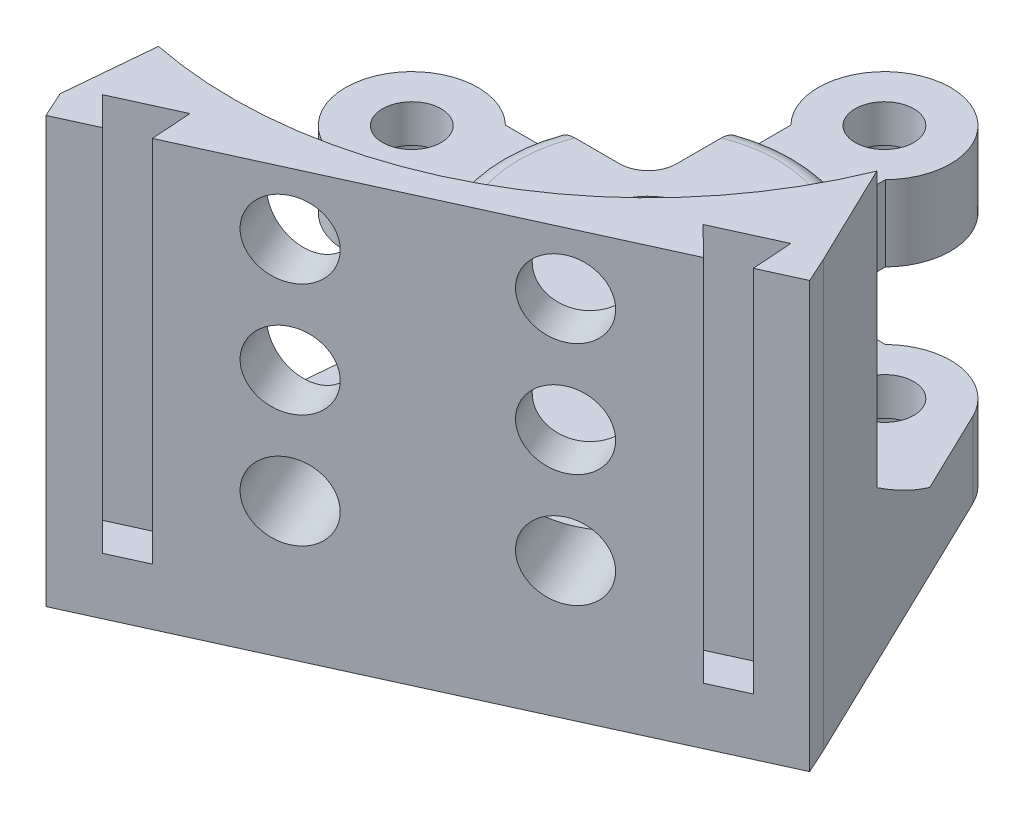
SolidWorks part; units mm, degrees
material "Nylon 6/10"
ref_plane "Front Plane" through (0, 0, 0) normal (0, 0, 1) x (1, 0, 0)
ref_plane "Top Plane" through (0, 0, 0) normal (0, 1, 0) x (1, 0, 0)
ref_plane "Right Plane" through (0, 0, 0) normal (1, 0, 0) x (0, 0, -1)
sketch "Sketch1" plane through (0, 0, 0) normal (0, 1, 0) x (1, 0, 0)
  line L0 (-5, 5) -> (-5, 25)
  line L1 (-25, -5) -> (-5, -5)
  line L2 (-25, -5) -> (-25, 5)
  line L3 (-25, 5) -> (-5, 5)
  line L4 (25, -5) -> (25, 5)
  line L5 (-25, -5) -> (25, 5) construction
  line L6 (-25, 5) -> (25, -5) construction
  line L7 (-5, -25) -> (5, -25)
  line L8 (-5, -25) -> (-5, -5)
  line L9 (-5, 25) -> (5, 25)
  line L10 (5, -25) -> (5, -5)
  line L11 (-5, -25) -> (5, 25) construction
  line L12 (-5, 25) -> (5, -25) construction
  line L13 (5, 5) -> (25, 5)
  line L14 (5, 5) -> (5, 25)
  line L15 (5, -5) -> (25, -5)
  point P0 (0, 0)
  point P6 (0, 0)
  dimension "D1" = 10
  dimension "D2" = 10
  dimension "D3" = 50
  dimension "D4" = 50
extrude "Boss-Extrude1" add sketch "Sketch1" along normal blind 8
sketch "Sketch2" plane through (0, 8, 0) normal (0, 1, 0) x (1, 0, 0)
  line L0 (25, -5) -> (25, 5) construction
  circle A0 centre (25, 0) radius 7
  circle A1 centre (0, -25) radius 7
  circle A2 centre (-25, 0) radius 7
  circle A3 centre (0, 25) radius 7
  point P13 (0, 0)
  dimension "D1" = 14
  dimension "D2" = 4
extrude "Boss-Extrude2" add sketch "Sketch2" against normal up to surface (8 mm away) up to face at (0, 0, 0)
sketch "Sketch3" plane through (0, 8, 0) normal (0, 1, 0) x (1, 0, 0)
  circle A0 centre (25, 0) radius 3.1
  circle A1 centre (0, -25) radius 3.1
  circle A2 centre (-25, 0) radius 3.1
  circle A3 centre (0, 25) radius 3.1
  point P12 (0, 0)
  dimension "D1" = 6.2
  dimension "D2" = 4
extrude "Cut-Extrude1" cut sketch "Sketch3" against normal up to surface (8 mm away) up to face at (0, 0, 0)
sketch "Sketch4" plane through (0, 0, 0) normal (0, 1, 0) x (1, 0, 0)
  circle A0 centre (25, 0) radius 5.05
  circle A1 centre (0, -25) radius 5.05
  circle A2 centre (-25, 0) radius 5.05
  circle A3 centre (0, 25) radius 5.05
  point P12 (0, 0)
  dimension "D1" = 10.1
  dimension "D2" = 4
extrude "Cut-Extrude4" cut sketch "Sketch4" along normal blind 4
sketch "Sketch5" plane through (0, 8, 0) normal (0, 1, 0) x (1, 0, 0)
  line L8 (5, 5) -> (5, 20.101)
  line L9 (-5, 20.101) -> (-5, 5)
  line L10 (-5, 5) -> (-20.101, 5)
  line L11 (-20.101, -5) -> (-5, -5)
  line L12 (-5, -5) -> (-5, -20.101)
  line L13 (5, -20.101) -> (5, -5)
  line L14 (5, -5) -> (20.101, -5)
  line L15 (20.101, 5) -> (5, 5)
  line L16 (5, 5) -> (5, 14.8825)
  line L17 (-5, 14.8825) -> (-5, 5)
  line L18 (-5, 5) -> (-14.8825, 5)
  line L19 (-14.8825, -5) -> (-5, -5)
  line L20 (-5, -5) -> (-5, -14.8825)
  line L21 (5, -14.8825) -> (5, -5)
  line L22 (5, -5) -> (14.8825, -5)
  line L23 (14.8825, 5) -> (5, 5)
  arc A0 (-14.8825, 5) -> (-14.8825, -5) centre (0, 0) ccw
  arc A1 (5, 14.8825) -> (-5, 14.8825) centre (0, 0) ccw
  arc A2 (14.8825, -5) -> (14.8825, 5) centre (0, 0) ccw
  arc A3 (-5, -14.8825) -> (5, -14.8825) centre (0, 0) ccw
  arc A5 (5, 20.101) -> (-5, 20.101) centre (0, 25) ccw
  arc A6 (-20.101, 5) -> (-20.101, -5) centre (-25, 0) ccw
  arc A7 (-5, -20.101) -> (5, -20.101) centre (0, -25) ccw
  arc A8 (20.101, -5) -> (20.101, 5) centre (25, 0) ccw
  dimension "D1" = 31.4
  dimension "D2" = 0
extrude "Boss-Extrude3" add sketch "Sketch5" along normal blind 2.5
sketch "Sketch6" plane through (0, 0, 0) normal (0, -1, 0) x (1, 0, 0)
  line L1 (-8.8, -8.8) -> (8.8, -8.8)
  line L2 (-8.8, -8.8) -> (-8.8, 8.8)
  line L3 (-8.8, 8.8) -> (8.8, 8.8)
  line L4 (8.8, -8.8) -> (8.8, 8.8)
  line L5 (-8.8, -8.8) -> (8.8, 8.8) construction
  line L6 (-8.8, 8.8) -> (8.8, -8.8) construction
  point P0 (0, 0)
  dimension "D1" = 17.6
  dimension "D2" = 90
extrude "Boss-Extrude4" add sketch "Sketch6" along normal blind 16
sketch "Sketch7" plane through (0, 10.5, 0) normal (0, 1, 0) x (1, 0, 0)
  circle A0 centre (0, 0) radius 5
  dimension "D1" = 10
extrude "Cut-Extrude5" cut sketch "Sketch7" against normal up to surface (26.5 mm away) up to face at (0, -16, 0)
fillet "Fillet1" radius 2 4 edges at (15.7, 10.5, 0) (0, 10.5, 15.7) (-15.7, 10.5, 0) (0, 10.5, -15.7)
sketch "Sketch8" plane through (0, 0, 0) normal (0, -1, 0) x (1, 0, 0)
  line L0 (-16.8381, 40.6507) -> (0, 0) construction
  line L1 (0, 0) -> (40.6507, 16.8381) construction
  line L2 (0, 0) -> (44, 0) construction
  line L3 (-9.5299, 52.6824) -> (45.9886, 27.4099)
  line L4 (18.2293, 40.0461) -> (0, 0) construction
  line L6 (8.8, 5) -> (20.101, 5) construction
  line L7 (5, 5) -> (8.8, 5) construction
  line L8 (5, 8.8) -> (5, 5) construction
  line L9 (5, 20.101) -> (5, 8.8) construction
  line L11 (8.8, 5) -> (20.101, 5)
  line L12 (5, 5) -> (8.8, 5)
  line L13 (5, 8.8) -> (5, 5)
  line L14 (5, 20.101) -> (5, 8.8)
  line L15 (-9.5299, 52.6824) -> (-6.9716, 24.37)
  line L18 (45.9886, 27.4099) -> (31.3052, -3.0404)
  circle A0 centre (0, 0) radius 44 construction
  arc A1 (-16.8381, 40.6507) -> (40.6507, 16.8381) centre (0, 0) cw construction
  arc A2 (20.101, -5) -> (20.101, 5) centre (25, 0) ccw construction
  arc A3 (5, 20.101) -> (-5, 20.101) centre (0, 25) ccw construction
  arc A4 (31.3052, -3.0404) -> (20.101, 5) centre (25, 0) ccw
  arc A5 (5, 20.101) -> (-6.9716, 24.37) centre (0, 25) ccw
  dimension "D1" = 88
  dimension "D2" = 90
  dimension "D3" = 22.5
  dimension "D4" = 61
extrude "Boss-Extrude5" add sketch "Sketch8" against normal up to surface (8 mm away) up to face at (-20.6709, 8, 0)
sketch "Sketch10" plane through (18.2293, 0, 40.0461) normal (0.4143, 0, 0.9101) x (0.9101, 0, -0.4143)
  line L0 (30.5, 8) -> (30.5, 0) construction
  line L1 (-30.5, 0) -> (30.5, 0)
  line L2 (-30.5, 0) -> (-30.5, 45)
  line L3 (-30.5, 45) -> (30.5, 45)
  line L4 (30.5, 0) -> (30.5, 45)
  dimension "D1" = 45
extrude "Boss-Extrude6" add sketch "Sketch10" along normal blind 3
sketch "Sketch11" plane through (0, 8, 0) normal (0, 1, 0) x (1, 0, 0)
  line L0 (31.3052, 3.0404) -> (45.9886, -27.4099) construction
  line L1 (-9.5299, -52.6824) -> (-6.9716, -24.37) construction
  line L2 (40.7611, -16.5691) -> (45.9886, -27.4099)
  line L3 (-9.5299, -52.6824) -> (-8.6675, -43.1379)
  line L4 (45.9886, -27.4099) -> (-9.5299, -52.6824) construction
  line L5 (45.9886, -27.4099) -> (-9.5299, -52.6824)
  circle A0 centre (0, 0) radius 44 construction
  arc A1 (40.7611, -16.5691) -> (-8.6675, -43.1379) centre (0, 0) cw
  line M6 (-6.9716, -24.37) -> (-9.5299, -52.6824)
  line M7 (-9.5299, -52.6824) -> (45.9886, -27.4099)
  line M8 (45.9886, -27.4099) -> (31.3052, 3.0404)
  dimension "D1" = 88
extrude "Boss-Extrude7" add sketch "Sketch11" along normal up to surface (37 mm away) contours A1 M7 M6 | A1 L5 M8 region at (-2.1231, 8, 46.5367) region at (37.7078, 8, 27.3197) up to face at (18.8508, 45, 41.4113)
sketch "Sketch12" plane through (0, 45, 0) normal (0, 1, 0) x (1, 0, 0)
  line L0 (19.4722, -42.7765) -> (10.8877, -23.9181) construction
  line L1 (47.2315, -30.1403) -> (-8.287, -55.4128) construction
  line L2 (-4.1914, -53.5484) -> (-7.2138, -50.5293)
  line L3 (-7.2138, -50.5293) -> (-0.8428, -47.6292)
  line L4 (-0.8428, -47.6292) -> (-0.5508, -51.8912)
  line L5 (-0.5508, -51.8912) -> (-4.1914, -53.5484)
  line L6 (-2.3711, -52.7198) -> (-5.4292, -46.0018) construction
  line L7 (41.3156, -32.8333) -> (38.2575, -26.1153) construction
  line L8 (39.4953, -33.6619) -> (43.1359, -32.0047)
  line L9 (36.4729, -30.6428) -> (39.4953, -33.6619)
  line L10 (42.8438, -27.7427) -> (36.4729, -30.6428)
  line L11 (43.1359, -32.0047) -> (42.8438, -27.7427)
  dimension "D1" = 24
  dimension "D3" = 7
  dimension "D2" = 4
  dimension "D4" = 3.5
  dimension "D5" = 4
extrude "Cut-Extrude6" cut sketch "Sketch12" against normal offset from surface (39 mm away) 6 up to face at (11.5974, 0, 19.2391)
fillet "Fillet3" radius 3 3 edges at (5, 5.25, -5) (-5, 5.25, -5) (-5, 5.25, 5)
sketch "Sketch13" plane through (19.4722, 0, 42.7765) normal (0.4143, 0, 0.9101) x (0.9101, 0, -0.4143)
  line L0 (0, 44.5069) -> (0, 0) construction
  line L1 (22, 45) -> (-22, 45) construction
  circle A0 centre (-11, 38.5) radius 4
  circle A1 centre (-11, 26.5) radius 4
  circle A2 centre (-11, 14.5) radius 4
  circle A3 centre (11, 14.5) radius 4
  circle A4 centre (11, 26.5) radius 4
  circle A5 centre (11, 38.5) radius 4
  dimension "D1" = 8
  dimension "D2" = 11
  dimension "D3" = 6.5
  dimension "D4" = 3
extrude "Cut-Extrude7" cut sketch "Sketch13" against normal up to surface (3.5604 mm away) up to face at (18.4394, 26.5, 34.3047)
chamfer "Chamfer1" distance 8 angle 45 1 edges at (20.8321, 8, 38.756)
fillet "Fillet4" radius 8.8 2 edges at (-8.8, -16, 0) (8.8, -16, 0)
ref_axis "Axis1" through (0, -7.2, -8.8) along (0, 0, 1)
sketch "Sketch14" plane through (0, 0, -8.8) normal (0, 0, -1) x (-1, 0, 0)
  circle A0 centre (0, -7.2) radius 2.4
  dimension "D1" = 4.8
extrude "Cut-Extrude8" cut sketch "Sketch14" against normal up to surface (17.6 mm away) up to face at (-0.8333, -5.6742, 8.8)
equation "\"D3@Sketch2\"= 50 - \"D2@Sketch2\""
